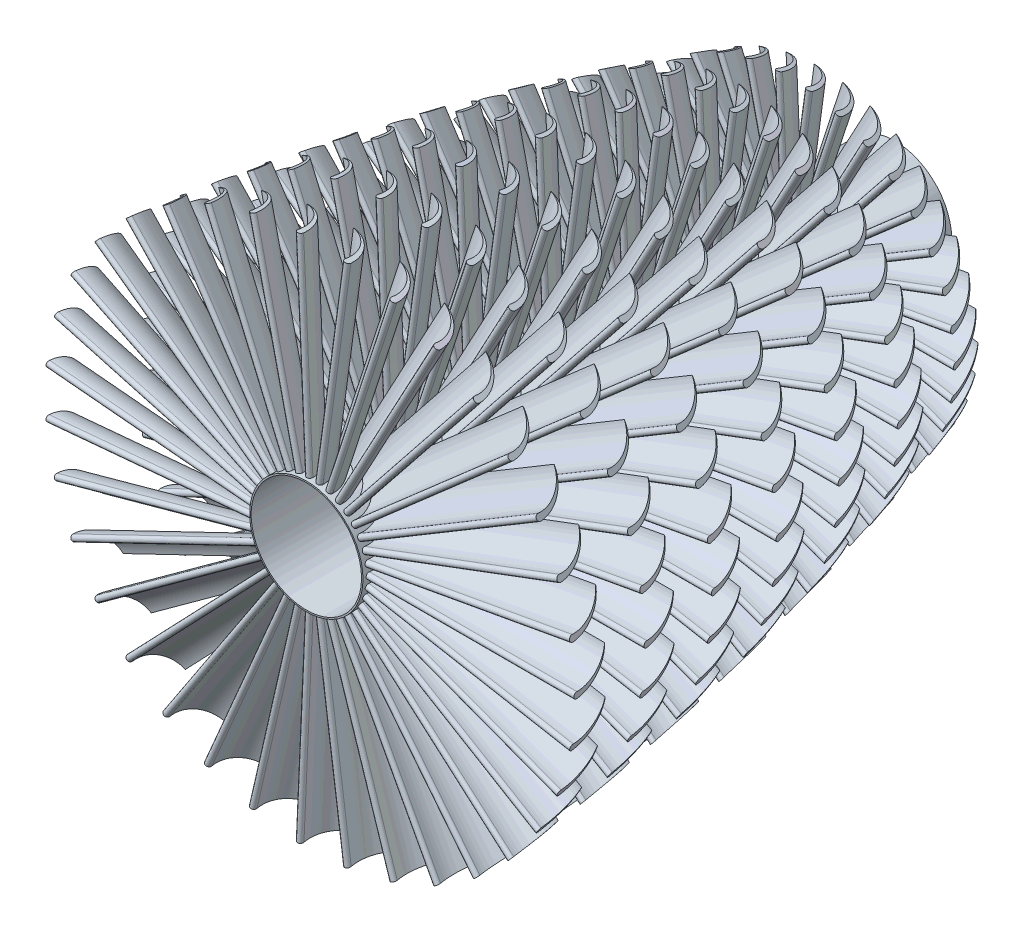
SolidWorks part; units mm, degrees
ref_plane "Front Plane" through (0, 0, 0) normal (0, 0, 1) x (1, 0, 0)
ref_plane "Top Plane" through (0, 0, 0) normal (0, 1, 0) x (1, 0, 0)
ref_plane "Right Plane" through (0, 0, 0) normal (1, 0, 0) x (0, 0, -1)
sketch "Sketch2" plane through (0, 0, 0) normal (0, 0, 1) x (1, 0, 0)
  circle A0 centre (0, 0) radius 7.5
  dimension "D1" = 15
extrude "Extrude-Thin3" add sketch "Sketch2" along normal blind 80 thin
ref_plane "Plane1" through (7.7, 0, 0) normal (1, 0, 0) x (0, 0, -1)
sketch "Sketch3" plane through (7.7, 0, 0) normal (1, 0, 0) x (0, 0, -1)
  line L0 (-79.58, 0) -> (-65.6926, 0) construction
  line L2 (-74.7144, 3.6491) -> (-74.7144, 3.4591)
  arc A0 (-79.1214, 0.4071) -> (-79.17, -0.41) centre (-79.17, 0) ccw
  arc A1 (-79.1214, 0.4071) -> (-74.7144, 3.6491) centre (-78.6473, 4.3789) ccw
  arc A2 (-79.17, -0.41) -> (-74.7144, 3.4591) centre (-79.17, 4.09) ccw
  point P13 (0, 0)
  point P15 (-74.9683, 2.2497)
  dimension "D1" = 0.82
  dimension "D4" = 4
  dimension "D5" = 4.5
  dimension "D3" = 0.19
ref_plane "Plane2" through (51.2, 0, 0) normal (1, 0, 0) x (0, 0, -1)
sketch "Sketch4" plane through (51.2, 0, 0) normal (1, 0, 0) x (0, 0, -1)
  line L0 (-74.7144, 3.6491) -> (-74.7144, 3.4591) construction
  line L1 (-74.7144, 3.6491) -> (-74.7144, 3.4591)
  arc A0 (-79.1214, 0.4071) -> (-74.7144, 3.6491) centre (-78.6473, 4.3789) ccw construction
  arc A1 (-79.1214, 0.4071) -> (-74.7144, 3.6491) centre (-78.6473, 4.3789) ccw
  arc A2 (-79.17, -0.41) -> (-74.7144, 3.4591) centre (-79.17, 4.09) ccw construction
  arc A3 (-79.17, -0.41) -> (-74.7144, 3.4591) centre (-79.17, 4.09) ccw
  arc A4 (-79.1214, 0.4071) -> (-79.17, -0.41) centre (-79.17, 0) ccw construction
  arc A5 (-79.1214, 0.4071) -> (-79.17, -0.41) centre (-79.17, 0) ccw
extrude "Boss-Extrude2" add sketch "Sketch4" against normal up to surface (44.4196 mm away) separate body
pattern_linear "LPattern1" count 7 spacing 10.75 along (0, 0, -1) of bodies 105
sketch "Sketch5" plane through (0, 0, 0) normal (0, 1, 0) x (1, 0, 0)
  line L0 (18, 0) -> (73.4178, 0)
  line L1 (73.4178, 0) -> (73.4178, -83.4902)
  line L2 (73.4178, -83.4902) -> (36.3, -83.4902)
  line L3 (0, 0) -> (0, -122.8583) construction
  line L4 (7.7, 0) -> (-7.7, 0) construction
  arc A0 (18, 0) -> (36.3, -83.4902) centre (-293.5568, -112.04) cw
  point P10 (18, 0)
  dimension "D3" = 331.09
  dimension "D1" = 18
  dimension "D2" = 36.3
revolve "Cut-Revolve1" cut sketch "Sketch5" angle 360 about L3
pattern_circular "CirPattern1" count 35 over 360 about axis through (0, 0, 0) along (0, 0, 1)
